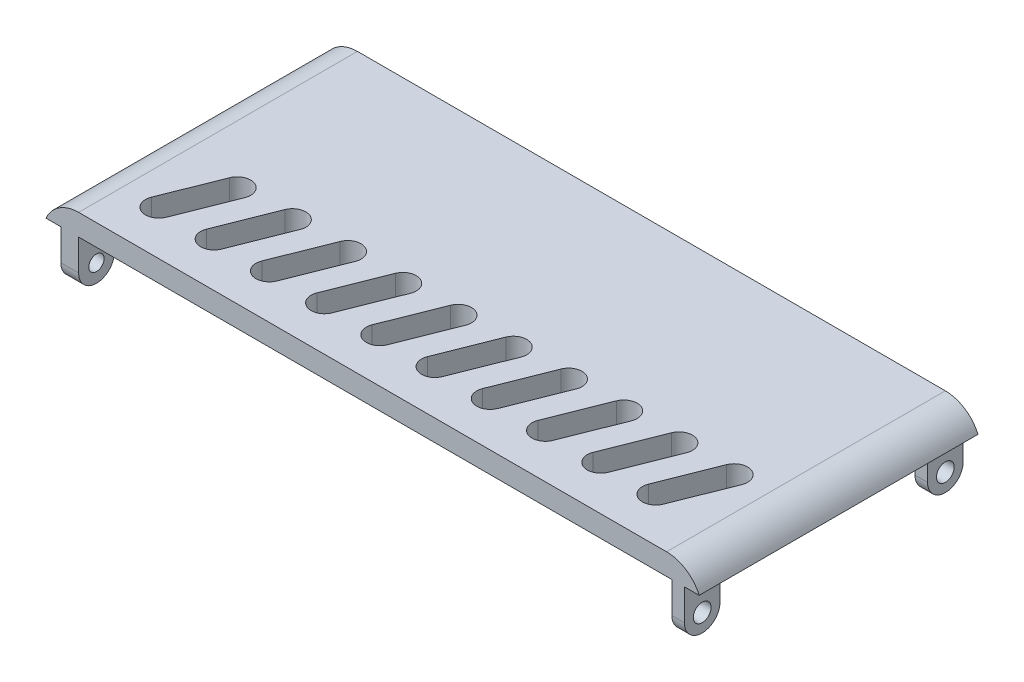
SolidWorks part; units mm, degrees
ref_plane "前视基准面" through (0, 0, 0) normal (0, 0, 1) x (1, 0, 0)
ref_plane "上视基准面" through (0, 0, 0) normal (0, 1, 0) x (1, 0, 0)
ref_plane "右视基准面" through (0, 0, 0) normal (1, 0, 0) x (0, 0, -1)
sketch "草图2" plane through (0, 0, 0) normal (0, 1, 0) x (1, 0, 0)
  line L0 (-27.0872, -11.4596) -> (-30.7532, -11.4596) construction
  line L1 (-31.0872, 19.8404) -> (42.9128, 19.8404)
  line L2 (-31.0872, 19.8404) -> (-31.0872, -11.4596)
  line L3 (-31.0872, -11.4596) -> (42.9128, -11.4596)
  line L4 (42.9128, 19.8404) -> (42.9128, -11.4596)
  dimension "D1" = 74
  dimension "D2" = 31.3
extrude "凸台-拉伸1" add sketch "草图2" along normal blind 4
fillet "圆角1" radius 4 2 edges at (-31.0872, 4, -4.1904) (42.9128, 4, -4.1904)
sketch "草图3" plane through (0, 0, -19.8404) normal (0, 0, -1) x (-1, 0, 0)
  line L1 (31.0872, 0) -> (-42.9128, 0)
  line L2 (31.0872, 0) -> (31.0872, 1.6)
  line L3 (31.0872, 1.6) -> (-42.9128, 1.6)
  line L4 (-42.9128, 0) -> (-42.9128, 1.6)
  dimension "D1" = 1.6
extrude "切除-拉伸1" cut sketch "草图3" against normal through all
sketch "草图19" plane through (0, 4, 0) normal (0, 1, 0) x (1, 0, 0)
  line L0 (-20.5872, -0.1596) -> (-23.0872, -6.4596) construction
  line L5 (-19.1929, -0.7128) -> (-21.6929, -7.0128)
  line L8 (-21.9814, 0.3937) -> (-24.4814, -5.9063)
  line L11 (38.9128, 19.8404) -> (-27.0872, 19.8404) construction
  line L14 (-27.0872, -11.4596) -> (38.9128, -11.4596) construction
  line L17 (-14.3872, -0.1596) -> (-16.8872, -6.4596) construction
  line L20 (-12.9929, -0.7128) -> (-15.4929, -7.0128)
  line L23 (-15.7814, 0.3937) -> (-18.2814, -5.9063)
  line L26 (-40.9597, 4.1904) -> (-18.0872, 4.1904) construction
  line L27 (-27.0872, 19.8404) -> (-27.0872, -11.4596) construction
  line L28 (-8.1872, -0.1596) -> (-10.6872, -6.4596) construction
  line L31 (-6.7929, -0.7128) -> (-9.2929, -7.0128)
  line L34 (-9.5814, 0.3937) -> (-12.0814, -5.9063)
  line L37 (-1.9872, -0.1596) -> (-4.4872, -6.4596) construction
  line L40 (-0.5929, -0.7128) -> (-3.0929, -7.0128)
  line L43 (-3.3814, 0.3937) -> (-5.8814, -5.9063)
  line L46 (4.2128, -0.1596) -> (1.7128, -6.4596) construction
  line L49 (5.6071, -0.7128) -> (3.1071, -7.0128)
  line L52 (2.8186, 0.3937) -> (0.3186, -5.9063)
  line L53 (10.4128, -0.1596) -> (7.9128, -6.4596) construction
  line L54 (11.8071, -0.7128) -> (9.3071, -7.0128)
  line L55 (9.0186, 0.3937) -> (6.5186, -5.9063)
  line L56 (16.6128, -0.1596) -> (14.1128, -6.4596) construction
  line L57 (18.0071, -0.7128) -> (15.5071, -7.0128)
  line L58 (15.2186, 0.3937) -> (12.7186, -5.9063)
  line L59 (22.8128, -0.1596) -> (20.3128, -6.4596) construction
  line L60 (24.2071, -0.7128) -> (21.7071, -7.0128)
  line L61 (21.4186, 0.3937) -> (18.9186, -5.9063)
  line L62 (29.0128, -0.1596) -> (26.5128, -6.4596) construction
  line L63 (30.4071, -0.7128) -> (27.9071, -7.0128)
  line L64 (27.6186, 0.3937) -> (25.1186, -5.9063)
  line L65 (35.2128, -0.1596) -> (32.7128, -6.4596) construction
  line L66 (36.6071, -0.7128) -> (34.1071, -7.0128)
  line L67 (33.8186, 0.3937) -> (31.3186, -5.9063)
  arc A32 (-19.1929, -0.7128) -> (-21.9814, 0.3937) centre (-20.5872, -0.1596) ccw
  arc A33 (-24.4814, -5.9063) -> (-21.6929, -7.0128) centre (-23.0872, -6.4596) ccw
  arc A34 (-12.9929, -0.7128) -> (-15.7814, 0.3937) centre (-14.3872, -0.1596) ccw
  arc A35 (-18.2814, -5.9063) -> (-15.4929, -7.0128) centre (-16.8872, -6.4596) ccw
  arc A36 (-6.7929, -0.7128) -> (-9.5814, 0.3937) centre (-8.1872, -0.1596) ccw
  arc A37 (-12.0814, -5.9063) -> (-9.2929, -7.0128) centre (-10.6872, -6.4596) ccw
  arc A38 (-0.5929, -0.7128) -> (-3.3814, 0.3937) centre (-1.9872, -0.1596) ccw
  arc A39 (-5.8814, -5.9063) -> (-3.0929, -7.0128) centre (-4.4872, -6.4596) ccw
  arc A40 (5.6071, -0.7128) -> (2.8186, 0.3937) centre (4.2128, -0.1596) ccw
  arc A41 (0.3186, -5.9063) -> (3.1071, -7.0128) centre (1.7128, -6.4596) ccw
  arc A42 (11.8071, -0.7128) -> (9.0186, 0.3937) centre (10.4128, -0.1596) ccw
  arc A43 (6.5186, -5.9063) -> (9.3071, -7.0128) centre (7.9128, -6.4596) ccw
  arc A44 (18.0071, -0.7128) -> (15.2186, 0.3937) centre (16.6128, -0.1596) ccw
  arc A45 (12.7186, -5.9063) -> (15.5071, -7.0128) centre (14.1128, -6.4596) ccw
  arc A46 (24.2071, -0.7128) -> (21.4186, 0.3937) centre (22.8128, -0.1596) ccw
  arc A47 (18.9186, -5.9063) -> (21.7071, -7.0128) centre (20.3128, -6.4596) ccw
  arc A48 (30.4071, -0.7128) -> (27.6186, 0.3937) centre (29.0128, -0.1596) ccw
  arc A49 (25.1186, -5.9063) -> (27.9071, -7.0128) centre (26.5128, -6.4596) ccw
  arc A50 (36.6071, -0.7128) -> (33.8186, 0.3937) centre (35.2128, -0.1596) ccw
  arc A51 (31.3186, -5.9063) -> (34.1071, -7.0128) centre (32.7128, -6.4596) ccw
  point P2 (-21.8372, -3.3096)
  point P15 (-15.6372, -3.3096)
  point P22 (-9.4372, -3.3096)
  point P29 (-3.2372, -3.3096)
  point P36 (2.9628, -3.3096)
  point P43 (9.1628, -3.3096)
  point P50 (15.3628, -3.3096)
  point P57 (21.5628, -3.3096)
  point P64 (-27.0872, 4.1904)
  point P68 (27.7628, -3.3096)
  point P75 (33.9628, -3.3096)
  dimension "D6" = 4
  dimension "D3" = 1.5
  dimension "D1" = 20
  dimension "D2" = 5
  dimension "D4" = 6.5
  dimension "D5" = 10
extrude "切除-拉伸6" cut sketch "草图19" against normal up to next
sketch "草图22" plane through (0, 1.6, 0) normal (0, -1, 0) x (1, 0, 0)
  line L0 (-30.7532, 11.4596) -> (42.5789, 11.4596) construction
  line L1 (-29.0872, 11.4596) -> (-27.0872, 11.4596)
  line L2 (-29.0872, 11.4596) -> (-29.0872, 7.4596)
  line L3 (-29.0872, 7.4596) -> (-27.0872, 7.4596)
  line L4 (-27.0872, 11.4596) -> (-27.0872, 7.4596)
  line L5 (-29.0872, 11.4596) -> (-29.0872, 1.1198) construction
  line L6 (-30.7532, -19.8404) -> (42.5789, -19.8404) construction
  line L7 (-27.0872, -19.8404) -> (-29.0872, -19.8404)
  line L8 (-27.0872, -19.8404) -> (-27.0872, -15.8404)
  line L9 (-27.0872, -15.8404) -> (-29.0872, -15.8404)
  line L10 (-29.0872, -19.8404) -> (-29.0872, -15.8404)
  line L11 (-29.0872, -5.8802) -> (-29.0872, -19.8404) construction
  line L12 (40.9128, 1.1198) -> (40.9128, 11.4596) construction
  line L13 (40.9128, 11.4596) -> (39.5128, 11.4596)
  line L14 (40.9128, 11.4596) -> (40.9128, 7.4596)
  line L15 (40.9128, 7.4596) -> (39.5128, 7.4596)
  line L16 (39.5128, 11.4596) -> (39.5128, 7.4596)
  line L18 (40.9128, -19.8404) -> (39.5128, -19.8404)
  line L19 (40.9128, -19.8404) -> (40.9128, -15.8404)
  line L20 (40.9128, -15.8404) -> (39.5128, -15.8404)
  line L21 (39.5128, -19.8404) -> (39.5128, -15.8404)
  point P26 (0, 0)
  point P27 (0, 0)
  point P29 (40.4304, -19.8404)
  point P30 (0, 0)
  point P31 (0, 0)
  point P32 (39.5093, 7.4596)
  point P33 (0, 0)
  point P34 (40.0196, -15.8404)
  dimension "D1" = 2
  dimension "D2" = 4
  dimension "D3" = 4
  dimension "D4" = 1.4
extrude "凸台-拉伸9" add sketch "草图22" along normal blind 5.5
fillet "圆角3" radius 2 8 edges at (-28.0872, -3.9, -19.8404) (-28.0872, -3.9, -15.8404) (-28.0872, -3.9, 7.4596) (-28.0872, -3.9, 11.4596) (40.2128, -3.9, -19.8404) (40.2128, -3.9, -15.8404) (40.2128, -3.9, 11.4596) (40.2128, -3.9, 7.4596)
sketch "草图23" plane through (-29.0872, 0, 0) normal (-1, 0, 0) x (0, 0, 1)
  circle A0 centre (9.4596, -1.9) radius 1
  circle A1 centre (-17.8404, -1.9) radius 1
  arc A2 (-17.8404, -3.9) -> (-15.8404, -1.9) centre (-17.8404, -1.9) ccw construction
  arc A3 (9.4596, -3.9) -> (11.4596, -1.9) centre (9.4596, -1.9) ccw construction
  dimension "D1" = 2
  dimension "D2" = 2
extrude "切除-拉伸9" cut sketch "草图23" against normal blind 2 draft 4
sketch "草图24" plane through (0, 1.6, 0) normal (0, -1, 0) x (1, 0, 0)
  line L0 (-27.0872, 11.4596) -> (39.5128, 11.4596) construction
  line L1 (-18.7532, 10.0596) -> (-14.7532, 10.0596)
  line L2 (-18.7532, 10.0596) -> (-18.7532, 8.0596)
  line L3 (-18.7532, 8.0596) -> (-14.7532, 8.0596)
  line L4 (-14.7532, 10.0596) -> (-14.7532, 8.0596)
  line L5 (30.5789, 8.0596) -> (26.5789, 8.0596)
  line L6 (30.5789, 8.0596) -> (30.5789, 10.0596)
  line L7 (30.5789, 10.0596) -> (26.5789, 10.0596)
  line L8 (26.5789, 8.0596) -> (26.5789, 10.0596)
  line L9 (42.5789, -19.8404) -> (42.5789, 11.4596) construction
  line L10 (-30.7532, 11.4596) -> (-30.7532, -19.8404) construction
  dimension "D1" = 3.4
  dimension "D2" = 2
  dimension "D3" = 12
  dimension "D4" = 4
  dimension "D5" = 12
  dimension "D6" = 4
extrude "凸台-拉伸10" add sketch "草图24" along normal blind 0.2
sketch "草图25" plane through (0, 1.6, 0) normal (0, -1, 0) x (1, 0, 0)
  text T0 "WHISPLAY" font "@Adobe Gothic Std B" height 3.5
extrude "切除-拉伸10" cut sketch "草图25" against normal blind 0.4
sketch "草图26" plane through (40.9128, 0, 0) normal (1, 0, 0) x (0, 0, -1)
  circle A1 centre (17.8404, -1.9) radius 1
  circle A2 centre (17.8404, -1.9) radius 1
  circle A3 centre (-9.4596, -1.9) radius 1
  circle A4 centre (-9.4596, -1.9) radius 1
  dimension "D1" = 0
  dimension "D2" = 0
extrude "切除-拉伸11" cut sketch "草图26" against normal blind 2 draft 4
sketch "草图27" plane through (0, 1.6, 0) normal (0, -1, 0) x (1, 0, 0)
  line L1 (-27.0872, 7.4596) -> (-24.2052, 7.4596)
  line L2 (-27.0872, 7.4596) -> (-27.0872, 8.1596)
  line L3 (-27.0872, 8.1596) -> (-24.2052, 8.1596)
  line L4 (-24.2052, 7.4596) -> (-24.2052, 8.1596)
  line L6 (39.5128, 7.4596) -> (33.8309, 7.4596)
  line L7 (39.5128, 7.4596) -> (39.5128, 8.1596)
  line L8 (39.5128, 8.1596) -> (33.8309, 8.1596)
  line L9 (33.8309, 7.4596) -> (33.8309, 8.1596)
  line L10 (-27.0872, 11.4596) -> (39.5128, 11.4596) construction
  arc A0 (-21.6929, 7.0128) -> (-24.4814, 5.9063) centre (-23.0872, 6.4596) ccw construction
  arc A1 (34.1071, 7.0128) -> (31.3186, 5.9063) centre (32.7128, 6.4596) ccw construction
  point P5 (0, 0)
  point P7 (33.8309, 7.9898)
  point P16 (0, 0)
  point P17 (33.8238, 7.4674)
  point P21 (0, 0)
  dimension "D1" = 3.3
extrude "凸台-拉伸11" add sketch "草图27" along normal blind 3
chamfer "倒角1" distance 1 angle 45 2 edges at (-25.6462, -1.4, 8.1596) (36.6718, -1.4, 8.1596)
